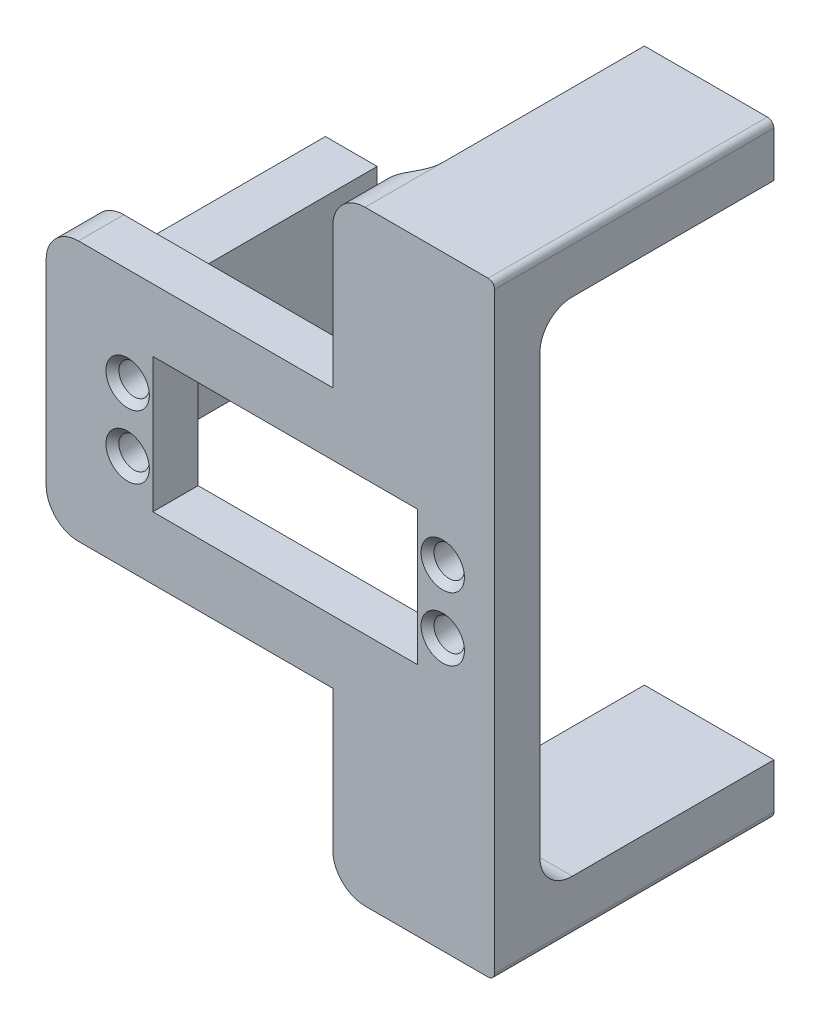
SolidWorks part; units mm, degrees
ref_plane "Front Plane" through (0, 0, 0) normal (0, 0, 1) x (1, 0, 0)
ref_plane "Top Plane" through (0, 0, 0) normal (0, 1, 0) x (1, 0, 0)
ref_plane "Right Plane" through (0, 0, 0) normal (1, 0, 0) x (0, 0, -1)
sketch "Sketch1" plane through (0, 0, 0) normal (1, 0, 0) x (0, 0, -1)
  line L1 (-10, 10) -> (10, 10)
  line L2 (-10, 10) -> (-10, -10)
  line L3 (-10, -10) -> (10, -10)
  line L4 (10, 10) -> (10, -10)
  line L5 (-10, 10) -> (10, -10) construction
  line L6 (-10, -10) -> (10, 10) construction
  point P0 (0, 0)
  dimension "D1" = 20
  dimension "D2" = 20
extrude "Boss-Extrude1" add sketch "Sketch1" along normal blind 20
sketch "Sketch2" plane through (20, 0, 0) normal (1, 0, 0) x (0, 0, -1)
  line L1 (-10, 20.1) -> (10, 20.1)
  line L2 (-10, 20.1) -> (-10, -20.1)
  line L3 (-10, -20.1) -> (10, -20.1)
  line L4 (10, 20.1) -> (10, -20.1)
  line L5 (-10, 20.1) -> (10, -20.1) construction
  line L6 (-10, -20.1) -> (10, 20.1) construction
  point P0 (0, 0)
  dimension "D1" = 20
  dimension "D2" = 40.2
extrude "Boss-Extrude2" add sketch "Sketch2" along normal blind 64.7
sketch "Sketch3" plane through (0, 0, 10) normal (0, 0, 1) x (1, 0, 0)
  line L1 (20, 20.1) -> (84.7, 20.1) construction
  line L2 (20, 20.1) -> (20, -20.1) construction
  line L3 (20, -20.1) -> (84.7, -20.1) construction
  line L4 (84.7, 20.1) -> (84.7, -20.1) construction
  line L5 (20, 20.1) -> (84.7, -20.1) construction
  line L6 (20, -20.1) -> (84.7, 20.1) construction
  line L7 (72.8, 10.4) -> (31.9, 10.4)
  line L8 (72.8, 10.4) -> (72.8, -10.4)
  line L9 (72.8, -10.4) -> (31.9, -10.4)
  line L10 (31.9, 10.4) -> (31.9, -10.4)
  line L11 (72.8, 10.4) -> (31.9, -10.4) construction
  line L12 (72.8, -10.4) -> (31.9, 10.4) construction
  point P4 (52.35, 0)
  point P7 (52.35, 0)
  dimension "D1" = 40.9
  dimension "D2" = 20.8
extrude "Cut-Extrude1" cut sketch "Sketch3" against normal through all
sketch "Sketch5" plane through (0, 0, 10) normal (0, 0, 1) x (1, 0, 0)
  line L0 (31.9, 0) -> (28.53, 0) construction
  line L5 (31.9, 10.4) -> (31.9, -10.4) construction
  line L7 (25.16, 0) -> (25.86, 0) construction
  line L8 (25.16, 9.4) -> (31.9, 9.4) construction
  line L9 (25.16, 9.4) -> (25.16, -9.4) construction
  line L10 (25.16, -9.4) -> (31.9, -9.4) construction
  line L11 (31.9, 9.4) -> (31.9, -9.4) construction
  line L12 (25.16, 9.4) -> (31.9, -9.4) construction
  line L13 (25.16, -9.4) -> (31.9, 9.4) construction
  line L14 (25.86, 0) -> (30.16, 0) construction
  line L15 (28.01, 0) -> (28.01, 9.4) construction
  line L16 (28.53, 9.4) -> (28.53, 7.1) construction
  line L17 (28.53, 7.1) -> (28.53, 2.7) construction
  line L18 (28.53, 2.7) -> (28.53, -2.7) construction
  line L19 (28.53, -2.7) -> (28.53, -7.1) construction
  line L20 (28.53, -7.1) -> (28.53, -9.4) construction
  line L21 (28.53, 4.9) -> (28.01, 4.9) construction
  line L22 (52.35, 10.4) -> (52.35, -10.4) construction
  line L23 (72.8, 10.4) -> (31.9, 10.4) construction
  line L24 (31.9, -10.4) -> (72.8, -10.4) construction
  circle A0 centre (28.01, 4.9) radius 2.35
  circle A1 centre (28.01, -4.9) radius 2.35
  circle A2 centre (76.69, -4.9) radius 2.35
  circle A3 centre (76.69, 4.9) radius 2.35
  dimension "D9" = 4.7
  dimension "D1" = 3.37
  dimension "D2" = 18.8
  dimension "D3" = 0.7
  dimension "D4" = 4.3
  dimension "D5" = 2.3
  dimension "D6" = 4.4
  dimension "D7" = 2.3
  dimension "D8" = 4.4
extrude "Cut-Extrude3" cut sketch "Sketch5" against normal blind 10
sketch "Sketch6" plane through (0, 0, 0) normal (-1, 0, 0) x (0, 0, 1)
  line L1 (10, 10) -> (-10, 10)
  line L2 (10, 10) -> (10, -10)
  line L3 (10, -10) -> (-10, -10)
  line L4 (-10, 10) -> (-10, -10)
  line L5 (10, 10) -> (-10, -10) construction
  line L6 (10, -10) -> (-10, 10) construction
  point P4 (0, 0)
extrude "Cut-Extrude4" cut sketch "Sketch6" against normal up to surface (20 mm away) up to face at (20, -15.05, 0)
chamfer "Chamfer1" distance 1 angle 45 4 edges at (79.04, -4.9, 10) (74.34, 4.9, 10) (30.36, 4.9, 10) (25.66, -4.9, 10)
sketch "Sketch7" plane through (0, 0, -10) normal (0, 0, -1) x (-1, 0, 0)
  line L1 (-10.6969, -24.7778) -> (-92.0937, -24.7778)
  line L2 (-10.6969, -24.7778) -> (-10.6969, 22.8141)
  line L3 (-10.6969, 22.8141) -> (-92.0937, 22.8141)
  line L4 (-92.0937, -24.7778) -> (-92.0937, 22.8141)
  line L5 (-10.6969, -24.7778) -> (-92.0937, 22.8141) construction
  line L6 (-10.6969, 22.8141) -> (-92.0937, -24.7778) construction
  point P4 (-51.3953, -0.9819)
extrude "Cut-Extrude5" cut sketch "Sketch7" against normal blind 13
sketch "Sketch8" plane through (20, 0, 0) normal (-1, 0, 0) x (0, 0, 1)
  line L1 (10, 20.1) -> (3, 20.1)
  line L2 (10, 20.1) -> (10, -20.1)
  line L3 (10, -20.1) -> (3, -20.1)
  line L4 (3, 20.1) -> (3, -20.1)
  line L5 (10, 20.1) -> (3, -20.1) construction
  line L6 (10, -20.1) -> (3, 20.1) construction
  point P4 (6.5, 0)
extrude "Boss-Extrude3" add sketch "Sketch8" along normal blind 4.58
sketch "Sketch9" plane through (0, 20.1, 0) normal (0, 1, 0) x (1, 0, 0)
  line L0 (15.42, -3) -> (84.7, -3) construction
  line L1 (84.7, -10) -> (59.7, -10)
  line L2 (84.7, -10) -> (84.7, -3)
  line L3 (84.7, -3) -> (59.7, -3)
  line L4 (59.7, -10) -> (59.7, -3)
  line L5 (84.7, -10) -> (59.7, -3) construction
  line L6 (84.7, -3) -> (59.7, -10) construction
  point P4 (72.2, -6.5)
  dimension "D1" = 25
extrude "Boss-Extrude4" add sketch "Sketch9" along normal blind 26.65
sketch "Sketch10" plane through (0, -20.1, 0) normal (0, -1, 0) x (1, 0, 0)
  line L0 (84.7, 3) -> (15.42, 3) construction
  line L1 (84.7, 10) -> (59.7, 10)
  line L2 (84.7, 10) -> (84.7, 3)
  line L3 (84.7, 3) -> (59.7, 3)
  line L4 (59.7, 10) -> (59.7, 3)
  line L5 (84.7, 10) -> (59.7, 3) construction
  line L6 (84.7, 3) -> (59.7, 10) construction
  point P4 (72.2, 6.5)
  dimension "D1" = 25
extrude "Boss-Extrude5" add sketch "Sketch10" along normal blind 26.65
sketch "Sketch11" plane through (0, 0, 3) normal (0, 0, -1) x (-1, 0, 0)
  line L0 (-15.42, 0) -> (-23.42, 0) construction
  line L1 (-84.7, 46.75) -> (-64.7, 46.75)
  line L2 (-84.7, 46.75) -> (-84.7, 38.75)
  line L3 (-84.7, 38.75) -> (-64.7, 38.75)
  line L4 (-64.7, 46.75) -> (-64.7, 38.75)
  line L5 (-84.7, 46.75) -> (-64.7, 38.75) construction
  line L6 (-84.7, 38.75) -> (-64.7, 46.75) construction
  line L7 (-84.7, -46.75) -> (-64.7, -46.75)
  line L8 (-84.7, -46.75) -> (-84.7, -38.75)
  line L9 (-84.7, -38.75) -> (-64.7, -38.75)
  line L10 (-64.7, -46.75) -> (-64.7, -38.75)
  line L11 (-84.7, -46.75) -> (-64.7, -38.75) construction
  line L12 (-84.7, -38.75) -> (-64.7, -46.75) construction
  line L13 (-15.42, 20.1) -> (-15.42, -20.1) construction
  line L15 (-15.42, 0) -> (-23.42, 0)
  line L16 (-15.42, 0) -> (-15.42, -10)
  line L17 (-15.42, -10) -> (-23.42, -10)
  line L18 (-23.42, 0) -> (-23.42, -10)
  line L19 (-15.42, 0) -> (-23.42, -10) construction
  line L20 (-15.42, -10) -> (-23.42, 0) construction
  line L21 (-15.42, 0) -> (-23.42, 0)
  line L22 (-15.42, 0) -> (-15.42, 10)
  line L23 (-15.42, 10) -> (-23.42, 10)
  line L24 (-23.42, 0) -> (-23.42, 10)
  line L25 (-15.42, 0) -> (-23.42, 10) construction
  line L26 (-15.42, 10) -> (-23.42, 0) construction
  point P4 (-74.7, 42.75)
  point P10 (-74.7, -42.75)
  point P19 (-19.42, -5)
  point P22 (-19.42, 5)
  line M18 (-84.7, 46.75) -> (-84.7, -46.75)
  line M19 (-84.7, -46.75) -> (-59.7, -46.75)
  line M22 (-15.42, -20.1) -> (-15.42, 20.1)
  line M25 (-59.7, 46.75) -> (-84.7, 46.75)
  dimension "D1" = 8
  dimension "D2" = 8
  dimension "D3" = 20
  dimension "D4" = 20
  dimension "D5" = 10
  dimension "D6" = 10
  dimension "D7" = 8
extrude "Boss-Extrude6" add sketch "Sketch11" along normal blind 36.14 contours L10 L9 M19 M18 | L4 L3 M25 M18 | L24 L15 L23 M22 | L15 L18 L17 M22 region at (74.7, -42.75, 3) region at (74.7, 42.75, 3) region at (19.42, -5, 3) region at (19.42, 5, 3)
sketch "Sketch12" plane through (0, 0, -33.14) normal (0, 0, -1) x (-1, 0, 0)
  line L0 (-19.42, 10) -> (-19.42, 6.7) construction
  line L1 (-15.42, 10) -> (-23.42, 10) construction
  line L2 (-15.42, 10) -> (-15.42, -10) construction
  line L3 (-15.42, -10) -> (-23.42, -10) construction
  line L4 (-23.42, 10) -> (-23.42, -10) construction
  line L5 (-15.42, 10) -> (-23.42, -10) construction
  line L6 (-15.42, -10) -> (-23.42, 10) construction
  line L7 (-19.42, 0) -> (-19.42, -10) construction
  line L8 (-19.42, 6.7) -> (-19.42, 2) construction
  line L9 (-19.42, 2) -> (-19.42, 0) construction
  line L10 (-19.42, 0) -> (-15.42, 0) construction
  line L11 (-64.7, -42.75) -> (-68, -42.75) construction
  line L12 (-64.7, -46.75) -> (-84.7, -46.75) construction
  line L13 (-64.7, -46.75) -> (-64.7, -38.75) construction
  line L14 (-64.7, -38.75) -> (-84.7, -38.75) construction
  line L15 (-84.7, -46.75) -> (-84.7, -38.75) construction
  line L16 (-64.7, -46.75) -> (-84.7, -38.75) construction
  line L17 (-64.7, -38.75) -> (-84.7, -46.75) construction
  line L18 (-68, -42.75) -> (-72.7, -42.75) construction
  line L19 (-72.7, -42.75) -> (-74.7, -42.75) construction
  line L20 (-74.7, -42.75) -> (-74.7, -46.75) construction
  line L21 (-23.42, 0) -> (-34.9452, 0) construction
  line L22 (-64.7, 42.75) -> (-84.7, 42.75) construction
  line L23 (-64.7, 46.75) -> (-64.7, 38.75) construction
  line L24 (-84.7, 46.75) -> (-84.7, 38.75) construction
  circle A2 centre (-19.42, 4.35) radius 2.35
  circle A3 centre (-19.42, -4.35) radius 2.35
  circle A4 centre (-70.35, -42.75) radius 2.35
  circle A5 centre (-79.05, -42.75) radius 2.35
  circle A6 centre (-79.05, 42.75) radius 2.35
  circle A7 centre (-70.35, 42.75) radius 2.35
  point P4 (-19.42, 0)
  point P21 (-74.7, -42.75)
  dimension "D1" = 4.7
  dimension "D2" = 2
  dimension "D3" = 4.7
  dimension "D6" = 4.7
  dimension "D4" = 4.7
  dimension "D5" = 2
extrude "Cut-Extrude6" cut sketch "Sketch12" against normal blind 10
chamfer "Chamfer2" distance 1 angle 45 6 edges at (70.35, 40.4, -33.14) (79.05, 45.1, -33.14) (79.05, -45.1, -33.14) (70.35, -40.4, -33.14) (19.42, -6.7, -33.14) (19.42, 6.7, -33.14)
fillet "Fillet1" radius 5 4 edges at (59.7, 46.75, 6.5) (59.7, -46.75, 6.5) (15.42, -20.1, 6.5) (15.42, 20.1, 6.5)
fillet "Fillet2" radius 1 2 edges at (84.7, -46.75, -11.57) (84.7, 46.75, -11.57)
fillet "Fillet3" radius 5 7 edges at (64.7, -42.75, 3) (74.7, -38.75, 3) (19.42, -10, 3) (23.42, 0, 3) (19.42, 10, 3) (64.7, 42.75, 3) (74.7, 38.75, 3)
